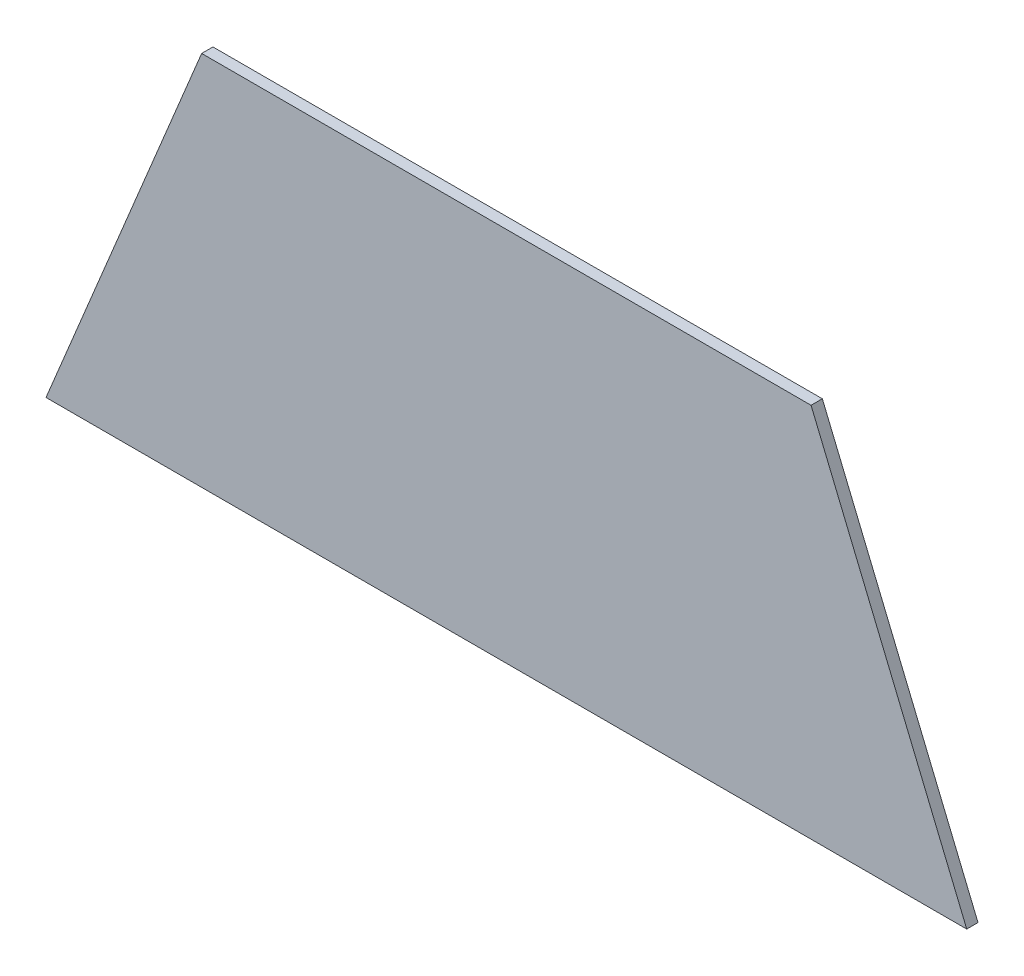
SolidWorks part; units mm, degrees
ref_plane "Front Plane" through (0, 0, 0) normal (0, 0, 1) x (1, 0, 0)
ref_plane "Top Plane" through (0, 0, 0) normal (0, 1, 0) x (1, 0, 0)
ref_plane "Right Plane" through (0, 0, 0) normal (1, 0, 0) x (0, 0, -1)
sketch "Sketch1" plane through (0, 0, 0) normal (0, 0, 1) x (1, 0, 0)
  line L0 (0, 0) -> (245, 0)
  line L3 (122.5, 0) -> (122.5, 100) construction
  line L5 (0, 0) -> (41.4214, 100)
  line L6 (245, 0) -> (203.5786, 100)
  line L7 (41.4214, 100) -> (203.5786, 100)
  point P3 (41.4214, 101.6376)
  point P9 (0, 0)
  point P10 (0, 0)
  point P11 (0, 0)
  point P12 (0, 0)
  point P13 (203.5786, 99.0085)
extrude "Boss-Extrude1" add sketch "Sketch1" along normal blind 3
